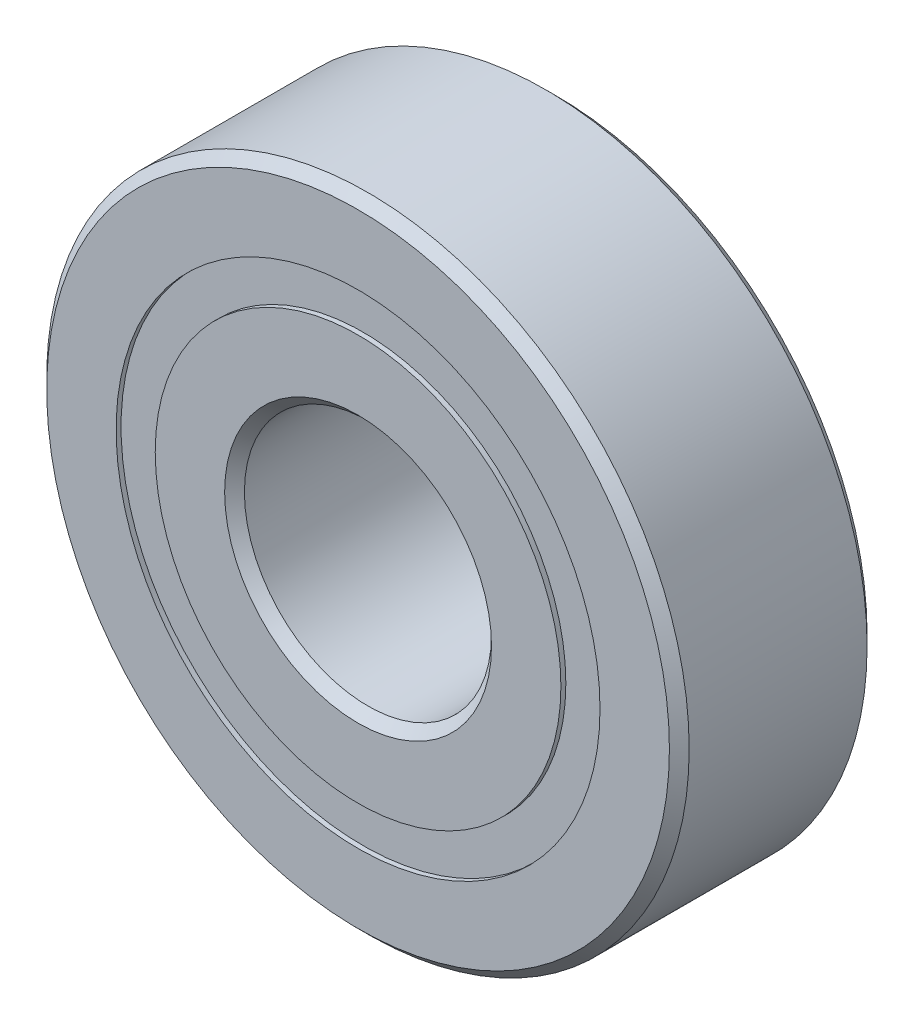
SolidWorks part; units mm, degrees
ref_plane "Front Plane" through (0, 0, 0) normal (0, 0, 1) x (1, 0, 0)
ref_plane "Top Plane" through (0, 0, 0) normal (0, 1, 0) x (1, 0, 0)
ref_plane "Right Plane" through (0, 0, 0) normal (1, 0, 0) x (0, 0, -1)
sketch "Sketch1" plane through (0, 0, 0) normal (1, 0, 0) x (0, 0, -1)
  line L0 (-4, 0) -> (4, 0) construction
  line L1 (0, 13) -> (0, -13) construction
  line L2 (3.6, 13) -> (-3.6, 13)
  line L3 (-3.6, 13) -> (-4, 12.6)
  line L4 (-4, 12.6) -> (-4, 9.7912)
  line L5 (-4, 9.7912) -> (-1.7778, 9.7912)
  line L6 (4, 9.7912) -> (1.7778, 9.7912)
  line L7 (4, 12.6) -> (4, 9.7912)
  line L8 (3.6, 13) -> (4, 12.6)
  line L9 (0, 13) -> (0, 9) construction
  line L10 (0, 9) -> (0, 5) construction
  arc A0 (-1.7778, 9.7912) -> (1.7778, 9.7912) centre (0, 9) cw
  point P14 (0, 5)
  dimension "Width" = 8
  dimension "OD" = 26
  dimension "D1" = 45
  dimension "D2" = 0.4
  dimension "Shaft Dia" = 10
  dimension "D3" = 3.5556
  dimension "D4" = 0.7912
revolve "Revolve1" add sketch "Sketch1" angle 360 about L0
sketch "Sketch3" plane through (0, 0, 0) normal (1, 0, 0) x (0, 0, -1)
  line L0 (-4, 8.2088) -> (-1.7778, 8.2088)
  line L1 (0, 13) -> (0, -13) construction
  line L2 (-4, 12.6) -> (-4, 9.7912) construction
  line L3 (-4, 8.2088) -> (-4, 5.4)
  line L4 (-3.6, 13) -> (-4, 12.6) construction
  line L5 (-4, 5.4) -> (-3.6, 5)
  line L6 (-3.6, 5) -> (3.6, 5)
  line L7 (3.6, 13) -> (3.6, -13) construction
  line L8 (3.6, 5) -> (4, 5.4)
  line L9 (4, -12.6) -> (4, 12.6) construction
  line L10 (4, 5.4) -> (4, 8.2088)
  line L11 (4, 8.2088) -> (1.7778, 8.2088)
  line L13 (3.6, 13) -> (4, 12.6) construction
  arc A0 (1.7778, 9.7912) -> (-1.7778, 9.7912) centre (0, 9) ccw construction
  arc A1 (1.7778, 8.2088) -> (-1.7778, 8.2088) centre (0, 9) cw
revolve "Revolve3" add sketch "Sketch3" angle 360 about L0
sketch "Sketch4" plane through (0, 0, 0) normal (1, 0, 0) x (0, 0, -1)
  line L0 (-1.9459, 9) -> (1.9459, 9)
  arc A2 (-1.9459, 9) -> (1.9459, 9) centre (0, 9) cw
  arc A3 (1.7778, 9.7912) -> (-1.7778, 9.7912) centre (0, 9) ccw construction
revolve "Revolve4" add sketch "Sketch4" angle 360 about L0
ref_axis "Axis1" through (0, 0, -4) along (0, 0, 1)
pattern_circular "CirPattern1" count 14 every 25.714 about axis through (0, 0, -4) along (0, 0, 1) of bodies 104
sketch "Sketch6" plane through (0, 0, 0) normal (1, 0, 0) x (0, 0, -1)
  line L0 (-4, 9.7912) -> (-1.7778, 9.7912) construction
  line L1 (-3.8, 9.7912) -> (-1.9459, 9.7912)
  line L2 (-3.8, 9.7912) -> (-3.8, 8.2088)
  line L3 (-3.8, 8.2088) -> (-1.9459, 8.2088)
  line L4 (-1.9459, 9.7912) -> (-1.9459, 8.2088)
  line L5 (-4, 8.2088) -> (-1.7778, 8.2088) construction
  line L6 (4, 9.7912) -> (1.7778, 9.7912) construction
  line L7 (3.8, 9.7912) -> (1.9459, 9.7912)
  line L8 (3.8, 9.7912) -> (3.8, 8.2088)
  line L9 (3.8, 8.2088) -> (1.9459, 8.2088)
  line L10 (1.9459, 9.7912) -> (1.9459, 8.2088)
  line L11 (4, 8.2088) -> (1.7778, 8.2088) construction
  line L12 (-3.6, 13) -> (-4, 12.6) construction
  point P18 (-3.8, 12.8)
revolve "Revolve5" add sketch "Sketch6" angle 360 about L0
equation "\"D2@Sketch1\" = \"Width@Sketch1\"*.05"
equation "\"D3@Sketch1\" = \"Width@Sketch1\"/2.25"
equation "\"D4@Sketch1\" = (((\"OD@Sketch1\"-\"Width@Sketch1\")/2)/3.25)/3.5"
equation "\"D2@CirPattern1\" = 360/\"Balls@CirPattern1\""
